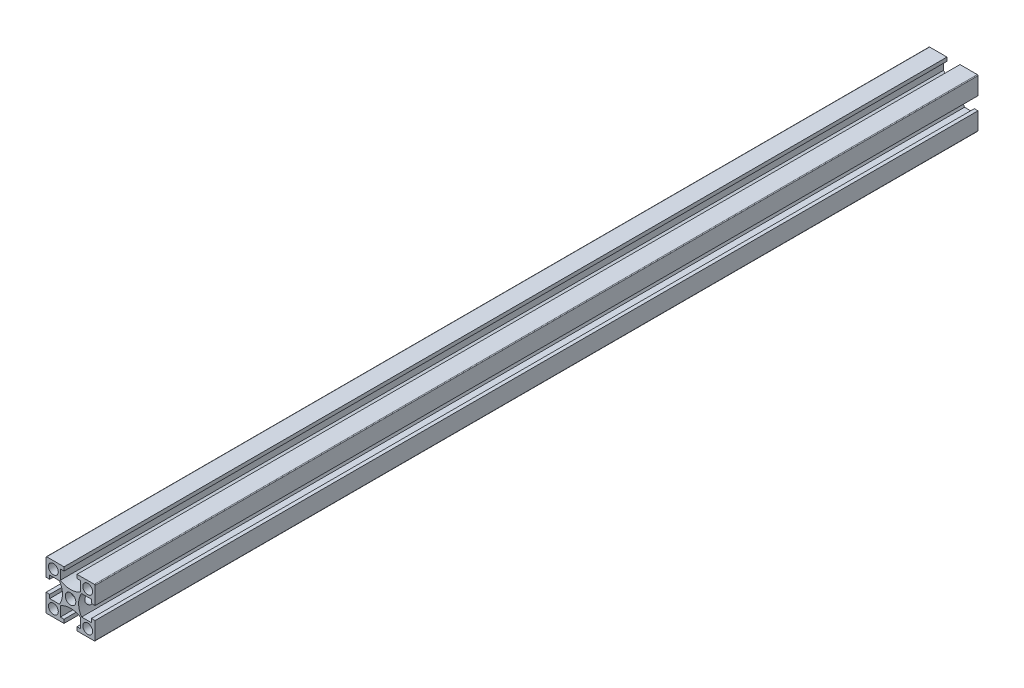
SolidWorks part; units mm, degrees
ref_plane "정면" through (0, 0, 0) normal (0, 0, 1) x (1, 0, 0)
ref_plane "윗면" through (0, 0, 0) normal (0, 1, 0) x (1, 0, 0)
ref_plane "우측면" through (0, 0, 0) normal (1, 0, 0) x (0, 0, -1)
sketch "스케치1" plane through (0, 0, 0) normal (0, 0, 1) x (1, 0, 0)
  line L0 (0, 32.0265) -> (0, -31.6588) construction
  line L1 (-10, 10) -> (-10, -10)
  line L2 (-10, 10) -> (10, 10)
  line L3 (-10, 2.65) -> (-8.5, 2.65)
  line L4 (13.6618, 0) -> (-11.6993, 0) construction
  line L5 (-8.5, 2.65) -> (-8.5, 4.15)
  line L6 (-8.5, 4.15) -> (-4.5032, 4.15)
  line L7 (-10, -2.65) -> (-8.5, -2.65)
  line L8 (-8.5, -2.65) -> (-8.5, -4.15)
  line L9 (-8.5, -4.15) -> (-4.5032, -4.15)
  line L10 (-10, -10) -> (10, -10)
  line L11 (10, 10) -> (10, -10)
  circle A0 centre (-7, 7) radius 2
  circle A1 centre (-7, -7) radius 2
  arc A2 (-4.5032, 4.15) -> (-4.5032, -4.15) centre (-11.0587, 0) cw
  circle A3 centre (0, 0) radius 2.15
  circle A4 centre (7, 7) radius 2
  circle A5 centre (7, -7) radius 2
  point P21 (-10, 0)
  point P23 (-3.3, 0)
  point P31 (0, -10)
  point P32 (0, 10)
  dimension "D3" = 4
  dimension "D9" = 6.7
  dimension "D10" = 4.3
  dimension "D11" = 7.7587
  dimension "D1" = 20
  dimension "D2" = 20
  dimension "D4" = 14
  dimension "D5" = 14
  dimension "D6" = 5.3
  dimension "D7" = 8.3
  dimension "D8" = 1.5
extrude "보스-돌출1" add sketch "스케치1" along normal blind 360 contours A0 | A4 | A3 | A5 | A1 | A2 L6 L5 L3 L1 L7 L8 L9 | L2 L11 L10 L1 region at (-6.6069, 0, 0) region at (-7, 7, 0) region at (-7, -7, 0) region at (0, 0, 0) region at (7, 7, 0) region at (7, -7, 0)
extrude "컷-돌출1" cut sketch "스케치1<3>" along normal up to next contours A2 L6 L5 L3 L1 L7 L8 L9 region at (-6.6069, 0, 0)
sketch "스케치1<3>" plane through (0, 0, 0) normal (0, 0, 1) x (1, 0, 0) same geometry as "스케치1"
pattern_circular "원형 패턴1" count 4 over 360 about axis through (0, 0, 360) along (0, 0, -1) of "컷-돌출1" reverse direction yes
fillet "필렛1" radius 0.3 4 edges at (10, -10, 180) (-10, -10, 180) (-10, 10, 180) (10, 10, 180)
sketch "스케치2" plane through (0, 0, 0) normal (1, 0, 0) x (0, 0, -1)
  line L0 (0, -2.65) -> (0, -9.7) construction
  line L1 (-360, 4.15) -> (-360, -4.15) construction
  circle A0 centre (-5, 0) radius 2.5
  circle A1 centre (-355, 0) radius 2.5
  dimension "D1" = 5
  dimension "D4" = 5
  dimension "D2" = 5
  dimension "D3" = 5
extrude "컷-돌출2" cut sketch "스케치2" against normal through all both and the other way through all contours A0 | A1
sketch "스케치3" plane through (10, 0, 0) normal (1, 0, 0) x (0, 0, -1)
  line L0 (-33.65, 9.7) -> (-33.65, -9.7) construction
  line L1 (0, 9.7) -> (-360, 9.7) construction
  line L2 (-360, -9.7) -> (0, -9.7) construction
  line L3 (-166.62, 9.7) -> (-166.62, -9.7) construction
  line L4 (-326.1, 9.7) -> (-326.1, -9.7) construction
  line L5 (0, -2.65) -> (0, -9.7) construction
  line L6 (-346.1, 9.7) -> (-346.1, -9.7) construction
  line L7 (-186.62, 9.7) -> (-186.62, -9.7) construction
  line L8 (-53.65, 9.7) -> (-53.65, -9.7) construction
  circle A0 centre (-64.65, 0) radius 2.5
  circle A1 centre (-155.62, 0) radius 2.5
  circle A2 centre (-197.62, 0) radius 2.5
  circle A3 centre (-315.1, 0) radius 2.5
  dimension "D7" = 11
  dimension "D8" = 11
  dimension "D1" = 33.65
  dimension "D2" = 166.62
  dimension "D3" = 326.1
  dimension "D10" = 11
  dimension "D5" = 20
  dimension "D4" = 20
  dimension "D6" = 20
extrude "컷-돌출3" [suppressed] cut sketch "스케치3" against normal through all
sketch "스케치4" plane through (10, 0, 0) normal (1, 0, 0) x (0, 0, -1)
  line L0 (-326.35, 9.7) -> (-326.35, -9.7) construction
  line L1 (0, 9.7) -> (-360, 9.7) construction
  line L2 (-360, -9.7) -> (0, -9.7) construction
  line L3 (-193.38, 9.7) -> (-193.38, -9.7) construction
  line L4 (-33.9, 9.7) -> (-33.9, -9.7) construction
  line L5 (-360, 9.7) -> (-360, 2.65) construction
  line L6 (-306.35, 9.7) -> (-306.35, -9.7) construction
  line L7 (-173.38, 9.7) -> (-173.38, -9.7) construction
  line L8 (-13.9, 9.7) -> (-13.9, -9.7) construction
  circle A0 centre (-295.35, 0) radius 2.5
  circle A1 centre (-204.38, 0) radius 2.5
  circle A2 centre (-162.38, 0) radius 2.5
  circle A3 centre (-44.9, 0) radius 2.5
  dimension "D7" = 11
  dimension "D1" = 33.65
  dimension "D2" = 166.62
  dimension "D3" = 326.1
  dimension "D8" = 11
  dimension "D9" = 11
  dimension "D10" = 11
  dimension "D4" = 20
  dimension "D5" = 20
  dimension "D6" = 20
extrude "컷-돌출4" cut sketch "스케치4" against normal through all
sketch "스케치5" plane through (0, -10, 0) normal (0, -1, 0) x (1, 0, 0)
  line L0 (4.15, 360) -> (-4.15, 360) construction
  circle A0 centre (0, 349) radius 2.5
  dimension "D1" = 11
extrude "컷-돌출5" cut sketch "스케치5" against normal through all
